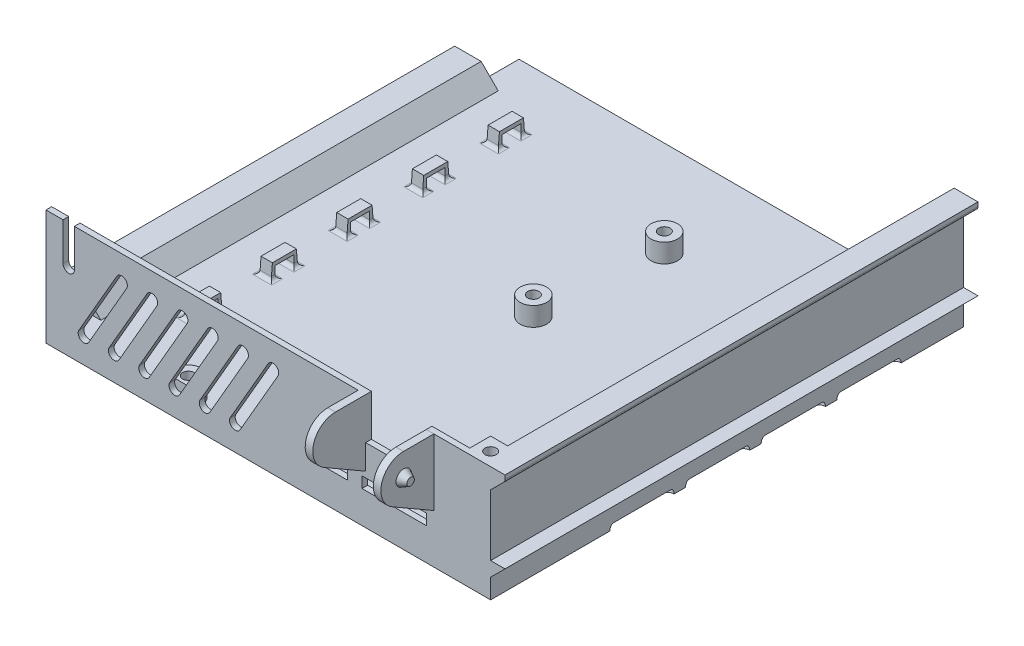
SolidWorks part; units mm, degrees
material "ABS"
ref_plane "Front Plane" through (0, 0, 0) normal (0, 0, 1) x (1, 0, 0)
ref_plane "Top Plane" through (0, 0, 0) normal (0, 1, 0) x (1, 0, 0)
ref_plane "Right Plane" through (0, 0, 0) normal (1, 0, 0) x (0, 0, -1)
ref_axis "Axis1" through (0, 0, 22) along (0, 0, -1)
sketch "Sketch1" plane through (0, 0, 0) normal (0, 1, 0) x (1, 0, 0)
  line L0 (-124.5, 0) -> (0, 0) construction
  line L1 (124.5, 0) -> (124.5, 125) construction
  line L2 (124.5, 125) -> (-124.5, 125) construction
  line L3 (-124.5, 125) -> (-124.5, 0) construction
  line L4 (40.75, 3.85) -> (40.75, 1.6) construction
  line L5 (38.5, 101.6) -> (108.5, 101.6)
  line L6 (38.5, 101.6) -> (38.5, 1.6)
  line L7 (38.5, 1.6) -> (108.5, 1.6)
  line L8 (108.5, 101.6) -> (108.5, 1.6)
  line L9 (38.5, 101.6) -> (108.5, 1.6) construction
  line L10 (38.5, 1.6) -> (108.5, 101.6) construction
  line L11 (40.75, 3.85) -> (38.5, 3.85) construction
  line L12 (-113.79, 77.51) -> (-116.04, 77.51) construction
  line L13 (77.7, 11.6) -> (86.7, 11.6)
  line L14 (77.7, 11.6) -> (77.7, 1.6)
  line L15 (77.7, 1.6) -> (86.7, 1.6)
  line L16 (86.7, 11.6) -> (86.7, 1.6)
  line L17 (77.7, 11.6) -> (86.7, 1.6) construction
  line L18 (77.7, 1.6) -> (86.7, 11.6) construction
  line L19 (90.5, 16.6) -> (107.5, 16.6)
  line L20 (90.5, 16.6) -> (90.5, 1.6)
  line L21 (90.5, 1.6) -> (107.5, 1.6)
  line L22 (107.5, 16.6) -> (107.5, 1.6)
  line L23 (90.5, 16.6) -> (107.5, 1.6) construction
  line L24 (90.5, 1.6) -> (107.5, 16.6) construction
  line L25 (-116.04, 113.59) -> (-92.96, 113.59)
  line L26 (-116.04, 113.59) -> (-116.04, 71.41)
  line L27 (-116.04, 71.41) -> (-92.96, 71.41)
  line L28 (-92.96, 113.59) -> (-92.96, 71.41)
  line L29 (-116.04, 113.59) -> (-92.96, 71.41) construction
  line L30 (-116.04, 71.41) -> (-92.96, 113.59) construction
  line L31 (-113.79, 77.51) -> (-113.79, 71.41) construction
  line L32 (-95.21, 107.49) -> (-95.21, 113.59) construction
  line L33 (-95.21, 107.49) -> (-92.96, 107.49) construction
  line L34 (-64.5, 85.45) -> (-68, 85.45) construction
  line L35 (-65, 88.95) -> (-15, 88.95)
  line L36 (-68, 85.95) -> (-68, 6.95)
  line L37 (-65, 3.95) -> (-15, 3.95)
  line L38 (-12, 85.95) -> (-12, 6.95)
  line L39 (-68, 88.95) -> (-12, 3.95) construction
  line L40 (-68, 3.95) -> (-12, 88.95) construction
  line L41 (-64.5, 85.45) -> (-15.5, 85.45) construction
  line L42 (-64.5, 85.45) -> (-64.5, 27.45) construction
  line L43 (-64.5, 27.45) -> (-15.5, 27.45) construction
  line L44 (-15.5, 85.45) -> (-15.5, 27.45) construction
  line L45 (0, 0) -> (0, 125) construction
  line L46 (0, 0) -> (124.5, 0) construction
  line L47 (-64.5, 85.45) -> (-64.5, 88.95) construction
  line L48 (73.5, 0.1) -> (73.5, 125) construction
  line L49 (-65.69, 22.9) -> (-49.81, 22.9)
  line L50 (-65.69, 22.9) -> (-65.69, 1.5)
  line L51 (-65.69, 1.5) -> (-49.81, 1.5)
  line L52 (-49.81, 22.9) -> (-49.81, 1.5)
  line L53 (-65.69, 22.9) -> (-49.81, 1.5) construction
  line L54 (-65.69, 1.5) -> (-49.81, 22.9) construction
  line L55 (-45.65, 19.42) -> (-32.35, 19.42)
  line L56 (-45.65, 19.42) -> (-45.65, 1.5)
  line L57 (-45.65, 1.5) -> (-32.35, 1.5)
  line L58 (-32.35, 19.42) -> (-32.35, 1.5)
  line L59 (-45.65, 19.42) -> (-32.35, 1.5) construction
  line L60 (-45.65, 1.5) -> (-32.35, 19.42) construction
  line L61 (-27.65, 19.42) -> (-14.35, 19.42)
  line L62 (-27.65, 19.42) -> (-27.65, 1.5)
  line L63 (-27.65, 1.5) -> (-14.35, 1.5)
  line L64 (-14.35, 19.42) -> (-14.35, 1.5)
  line L65 (-27.65, 19.42) -> (-14.35, 1.5) construction
  line L66 (-27.65, 1.5) -> (-14.35, 19.42) construction
  line L67 (-40, 0) -> (-40, 125) construction
  line L68 (-113.79, 11.41) -> (-113.79, 17.51) construction
  line L69 (-116.04, 53.59) -> (-92.96, 53.59)
  line L70 (-116.04, 53.59) -> (-116.04, 11.41)
  line L71 (-116.04, 11.41) -> (-92.96, 11.41)
  line L72 (-92.96, 53.59) -> (-92.96, 11.41)
  line L73 (-116.04, 53.59) -> (-92.96, 11.41) construction
  line L74 (-116.04, 11.41) -> (-92.96, 53.59) construction
  line L75 (-113.79, 17.51) -> (-116.04, 17.51) construction
  line L76 (-95.21, 53.59) -> (-95.21, 47.49) construction
  line L77 (-95.21, 47.49) -> (-92.96, 47.49) construction
  line L78 (-104.5, 0) -> (-104.5, 32.5) construction
  line L79 (-104.5, 32.5) -> (-104.5, 92.5) construction
  line L80 (-104.5, 92.5) -> (-104.5, 125) construction
  line L81 (-64.5, 27.45) -> (-15.5, 85.45) construction
  line L82 (-15.5, 27.45) -> (-64.5, 85.45) construction
  circle A0 centre (105.5, 81.6) radius 1.75
  circle A1 centre (105.5, 19.6) radius 1.75
  circle A2 centre (70.6, 99.8) radius 1.75
  circle A3 centre (67.8, 68) radius 1.75
  circle A4 centre (40.75, 3.85) radius 1.75
  circle A5 centre (-95.21, 107.49) radius 1.4
  circle A6 centre (-113.79, 77.51) radius 1.4
  arc A7 (-15, 3.95) -> (-12, 6.95) centre (-15, 6.95) ccw
  arc A8 (-68, 6.95) -> (-65, 3.95) centre (-65, 6.95) ccw
  arc A9 (-15, 88.95) -> (-12, 85.95) centre (-15, 85.95) cw
  arc A10 (-65, 88.95) -> (-68, 85.95) centre (-65, 85.95) ccw
  circle A11 centre (-64.5, 85.45) radius 1.375
  circle A12 centre (-15.5, 85.45) radius 1.375
  circle A13 centre (-64.5, 27.45) radius 1.375
  circle A14 centre (-15.5, 27.45) radius 1.375
  circle A15 centre (-95.21, 47.49) radius 1.4
  circle A16 centre (-113.79, 17.51) radius 1.4
  circle A17 centre (40.75, 3.85) radius 2.84
  point P0 (73.5, 51.6)
  point P3 (-104.5, 92.5)
  point P4 (0, 0)
  point P24 (82.2, 6.6)
  point P30 (99, 9.1)
  point P47 (-40, 46.45)
  point P65 (-39, 10.46)
  point P69 (-57.75, 12.2)
  point P84 (-21, 10.46)
  point P89 (-104.5, 32.5)
  point P111 (-40, 56.45)
  dimension "D5" = 3.5
  dimension "D26" = 3
  dimension "D27" = 2.75
  dimension "D44" = 2.8
  dimension "D49" = 5.68
  dimension "D1" = 249
  dimension "D2" = 125
  dimension "D3" = 100
  dimension "D4" = 70
  dimension "D6" = 20
  dimension "D7" = 3
  dimension "D8" = 82
  dimension "D9" = 1.8
  dimension "D10" = 37.9
  dimension "D11" = 33.6
  dimension "D12" = 40.7
  dimension "D13" = 2.25
  dimension "D14" = 9
  dimension "D15" = 10
  dimension "D16" = 26.3
  dimension "D17" = 17
  dimension "D18" = 15
  dimension "D19" = 9.5
  dimension "D20" = 23.08
  dimension "D21" = 42.18
  dimension "D22" = 6.1
  dimension "D23" = 2.25
  dimension "D24" = 85
  dimension "D25" = 56
  dimension "D28" = 58
  dimension "D29" = 49
  dimension "D30" = 10.25
  dimension "D31" = 29
  dimension "D32" = 47
  dimension "D33" = 21.4
  dimension "D34" = 15.88
  dimension "D35" = 2.45
  dimension "D36" = 13.3
  dimension "D37" = 17.92
  dimension "D38" = 2.45
  dimension "D39" = 2.45
  dimension "D40" = 2.25
  dimension "D41" = 1.6
  dimension "D42" = 40
  dimension "D43" = 1.5
  dimension "D45" = 60
  dimension "D46" = 3.5
  dimension "D47" = 20
  dimension "D48" = 16
sketch "Sketch2" plane through (0, 0, 0) normal (0, 1, 0) x (1, 0, 0)
  line L0 (124.5, 125) -> (-124.5, 125) construction
  line L1 (124.5, 0) -> (7, 0)
  line L2 (124.5, 0) -> (124.5, 125)
  line L3 (124.5, 125) -> (7, 125)
  line L4 (7, 0) -> (7, 125)
  line L5 (124.5, 0) -> (7, 125) construction
  line L6 (124.5, 125) -> (7, 0) construction
  point P4 (65.75, 62.5)
  dimension "D1" = 7
extrude "Boss-Extrude1" add sketch "Sketch2" along normal blind 2.5
sketch "Sketch3" plane through (0, 2.5, 0) normal (0, 1, 0) x (1, 0, 0)
  circle A0 centre (105.5, 19.6) radius 1.5
  circle A1 centre (67.8, 68) radius 1.5
  circle A2 centre (105.5, 81.6) radius 1.5
  circle A3 centre (70.6, 99.8) radius 1.5
  circle A4 centre (40.75, 3.85) radius 1.5
  circle A5 centre (40.75, 3.85) radius 3.5
  circle A6 centre (105.5, 19.6) radius 3.5
  circle A7 centre (67.8, 68) radius 3.5
  circle A8 centre (105.5, 81.6) radius 3.5
  circle A9 centre (70.6, 99.8) radius 3.5
  dimension "D1" = 3
  dimension "D2" = 2
extrude "Boss-Extrude2" add sketch "Sketch3" along normal blind 5
sketch "Sketch5" plane through (0, 2.5, 0) normal (0, 1, 0) x (1, 0, 0)
  line L0 (124.5, 0) -> (124.5, 125) construction
  line L1 (7, 0) -> (124.5, 0)
  line L2 (7, 0) -> (7, 1.5)
  line L3 (7, 1.5) -> (124.5, 1.5)
  line L4 (124.5, 0) -> (124.5, 1.5)
  line L5 (7, 0) -> (124.5, 1.5) construction
  line L6 (7, 1.5) -> (124.5, 0) construction
  point P4 (65.75, 0.75)
  dimension "D1" = 1.5
extrude "Boss-Extrude3" add sketch "Sketch5" along normal blind 28
sketch "Sketch6" plane through (0, 0, 0) normal (0, 0, 1) x (1, 0, 0)
  line L0 (77.7, 0) -> (86.7, 0) construction
  line L1 (77.7, 0) -> (86.7, 0) construction
  line L2 (90.5, 0) -> (107.5, 0) construction
  line L3 (90.5, 0) -> (107.5, 0) construction
  line L4 (77.7, 0) -> (77.7, 2.5) construction
  line L5 (77.7, 2.5) -> (77.7, 7.5) construction
  line L6 (77.7, 7.5) -> (77.7, 8.5) construction
  line L7 (77.7, 8.5) -> (86.7, 8.5)
  line L8 (86.7, 8.5) -> (86.7, 13.6)
  line L9 (86.7, 13.6) -> (77.7, 13.6)
  line L10 (77.7, 13.6) -> (77.7, 8.5)
  line L11 (90.5, 8.5) -> (107.5, 8.5)
  line L12 (107.5, 8.5) -> (107.5, 11.4)
  line L13 (107.5, 11.4) -> (90.5, 11.4)
  line L14 (90.5, 11.4) -> (90.5, 8.5)
  line L15 (77.7, 8.5) -> (86.7, 13.6) construction
  line L16 (77.7, 13.6) -> (86.7, 8.5) construction
  line L18 (76.45, 15.8) -> (87.95, 15.8) construction
  line L19 (76.45, 15.8) -> (76.45, 6.3) construction
  line L20 (76.45, 6.3) -> (87.95, 6.3) construction
  line L21 (87.95, 15.8) -> (87.95, 6.3) construction
  line L22 (76.45, 15.8) -> (87.95, 6.3) construction
  line L23 (76.45, 6.3) -> (87.95, 15.8) construction
  point P9 (82.2, 11.05)
  dimension "D1" = 2.5
  dimension "D2" = 5
  dimension "D3" = 1
  dimension "D4" = 9
  dimension "D5" = 17
  dimension "D6" = 2.9
  dimension "D7" = 5.1
  dimension "D8" = 11.5
  dimension "D9" = 9.5
extrude "Cut-Extrude1" cut sketch "Sketch6" against normal up to surface (1.5 mm away) up to face at (53.25, 10.75, -1.5)
sketch "Sketch7" plane through (0, 0, 0) normal (0, 0, 1) x (1, 0, 0)
  line L0 (124.5, 0) -> (124.5, 5.2)
  line L1 (124.5, 30.5) -> (124.5, 0) construction
  line L2 (124.5, 5.2) -> (126.3, 7)
  line L3 (126.3, 7) -> (126.3, 0) construction
  line L4 (126.3, 0) -> (124.5, 0) construction
  line L5 (126.3, 7) -> (122, 7)
  line L6 (122, 7) -> (122, 0)
  line L7 (7, 0) -> (124.5, 0) construction
  line L8 (122, 0) -> (124.5, 0)
  line L9 (124.5, 7) -> (124.5, 25.2)
  line L10 (126.3, 7) -> (126.3, 27) construction
  line L11 (124.5, 25.2) -> (126.3, 27)
  line L12 (126.3, 0) -> (128.3, 0) construction
  line L13 (128.3, 0) -> (128.3, 29) construction
  line L14 (126.3, 7) -> (128.3, 9)
  line L15 (126.3, 27) -> (128.3, 29)
  line L16 (122, 7) -> (122, 30.5)
  line L17 (7, 30.5) -> (124.5, 30.5) construction
  line L18 (122, 30.5) -> (128.3, 30.5)
  line L19 (128.3, 30.5) -> (128.3, 29)
  line L20 (128.3, 9) -> (122, 9)
  line M19 (7, 0) -> (124.5, 0)
  line M20 (124.5, 0) -> (124.5, 30.5)
  line M21 (124.5, 30.5) -> (7, 30.5)
  dimension "D1" = 5.2
  dimension "D2" = 7
  dimension "D3" = 1.8
  dimension "D4" = 2.5
  dimension "D5" = 25.2
  dimension "D6" = 27
  dimension "D7" = 2
extrude "Boss-Extrude4" add sketch "Sketch7" against normal up to surface (125 mm away) contours L5 L6 M19 M20 | L2 L5 M20 | L14 L20 L5 M20 | L20 L16 L5 M20 | L20 L9 L16 M20 M21 | L19 L18 L11 L15 M20 region at (123.25, 3.5, 0) region at (125.1, 6.4, 0) region at (125.9595, 8.119, 0) region at (123.25, 8, 0) region at (123.25, 19.75, 0) region at (126.0461, 28.623, 0) up to face at (65.75, 1.25, -125)
fillet "Fillet1" radius 1 1 edges at (128.3, 29, -62.5)
sketch "Sketch9" plane through (0, 0, 0) normal (0, 0, 1) x (1, 0, 0)
  line L0 (7, 7) -> (11.5, 2.5)
  line L1 (7, 0) -> (0, 0)
  line L2 (7, 0) -> (7, 7)
  line L3 (7, 7) -> (0, 7)
  line L4 (0, 0) -> (0, 7)
  line L5 (7, 0) -> (0, 7) construction
  line L6 (7, 7) -> (0, 0) construction
  line L7 (11.5, 2.5) -> (7, 2.5)
  line L8 (7, 0) -> (124.5, 0) construction
  circle A0 centre (3.5, 3.5) radius 1.5
  point P4 (3.5, 3.5)
  line M15 (7, 30.5) -> (7, 0)
  dimension "D2" = 3
  dimension "D1" = 7
  dimension "D3" = 2.5
  dimension "D4" = 45
extrude "Boss-Extrude5" add sketch "Sketch9" against normal offset from surface (105 mm away) 10 from offset 10 contours L4 L1 L2 L3 A0 M15 | L7 L0 M15 region at (8.5, 4, 0) region at (6.901, 4.75, 0) up to face at (105.7481, 14.3743, -125) offset against normal yes
sketch "Sketch12" plane through (0, 30.5, 0) normal (0, 1, 0) x (1, 0, 0)
  line L1 (124.5, 0) -> (117.5, 0)
  line L2 (124.5, 0) -> (124.5, 7)
  line L3 (124.5, 7) -> (117.5, 7)
  line L4 (117.5, 0) -> (117.5, 7)
  line L5 (124.5, 0) -> (117.5, 7) construction
  line L6 (124.5, 7) -> (117.5, 0) construction
  circle A0 centre (121, 3.5) radius 1.5 construction
  point P4 (121, 3.5)
  dimension "D2" = 3
  dimension "D1" = 7
extrude "Boss-Extrude7" add sketch "Sketch12" against normal up to surface (28 mm away) up to face at (37.65, 2.5, -51.185)
sketch "Sketch13" plane through (0, 30.5, 0) normal (0, 1, 0) x (1, 0, 0)
  circle A0 centre (121, 3.5) radius 1.5 construction
  circle A1 centre (121, 3.5) radius 1.5
extrude "Cut-Extrude3" cut sketch "Sketch13" against normal blind 10
sketch "Sketch15" plane through (0, 0, 0) normal (-1, 0, 0) x (0, 0, 1)
  line L0 (-125, 2.5) -> (-1.5, 2.5) construction
  line L1 (-107.5, 2.5) -> (-108.5, 2.5)
  line L2 (-107.5, 2.5) -> (-102.5, 2.5) construction
  line L3 (-107.5, 2.5) -> (-107.5, 5.5)
  line L4 (-107.5, 5.5) -> (-102.5, 5.5)
  line L5 (-102.5, 2.5) -> (-102.5, 5.5)
  line L6 (-107.5, 2.5) -> (-102.5, 5.5) construction
  line L7 (-107.5, 5.5) -> (-102.5, 2.5) construction
  line L8 (-108.5, 2.5) -> (-108.1701, 6.5)
  line L9 (-108.1701, 6.5) -> (-101.8299, 6.5)
  line L10 (-101.8299, 6.5) -> (-101.5, 2.5)
  line L11 (-101.5, 2.5) -> (-102.5, 2.5)
  line L12 (-115, 7) -> (-115, 0) construction
  point P8 (-105, 4)
  dimension "D1" = 3
  dimension "D2" = 5
  dimension "D3" = 1
  dimension "D4" = 1
  dimension "D5" = 0.75
  dimension "D6" = 10
extrude "Boss-Extrude8" add sketch "Sketch15" along normal blind 3 from offset 25 offset against normal yes
pattern_linear "LPattern1" count 5 spacing 20 along (0, 0, 1) of "Boss-Extrude8"
fillet "Fillet2" radius 1 40 edges at (25, 2.5, -62) (23.5, 2.5, -62.5) (23.5, 2.5, -61.5) (22, 2.5, -62) (25, 2.5, -68) (22, 2.5, -68) (23.5, 2.5, -67.5) (23.5, 2.5, -68.5) (25, 2.5, -82) (23.5, 2.5, -82.5) (23.5, 2.5, -81.5) (22, 2.5, -82) (25, 2.5, -88) (23.5, 2.5, -88.5) (23.5, 2.5, -87.5) (22, 2.5, -88) (25, 2.5, -102) (23.5, 2.5, -102.5) (23.5, 2.5, -101.5) (22, 2.5, -102) (25, 2.5, -108) (23.5, 2.5, -108.5) (23.5, 2.5, -107.5) (22, 2.5, -108) (25, 2.5, -22) (23.5, 2.5, -22.5) (23.5, 2.5, -21.5) (22, 2.5, -22) (25, 2.5, -28) (23.5, 2.5, -28.5) (23.5, 2.5, -27.5) (22, 2.5, -28) (25, 2.5, -42) (23.5, 2.5, -42.5) (23.5, 2.5, -41.5) (22, 2.5, -42) (25, 2.5, -48) (23.5, 2.5, -48.5) (23.5, 2.5, -47.5) (22, 2.5, -48)
sketch "Sketch16" plane through (0, 0, 0) normal (0, 0, 1) x (1, 0, 0)
  line L0 (27, 23.9103) -> (17, 6.5897) construction
  line L1 (28.299, 23.1603) -> (18.299, 5.8397)
  line L2 (25.701, 24.6603) -> (15.701, 7.3397)
  line L3 (17, 6.5897) -> (27, 6.5897) construction
  line L4 (27, 6.5897) -> (27, 23.9103) construction
  line L5 (7, 15.25) -> (124.5, 15.25) construction
  line L6 (7, 30.5) -> (7, 0) construction
  line L7 (124.5, 25.2) -> (124.5, 9) construction
  arc A0 (28.299, 23.1603) -> (25.701, 24.6603) centre (27, 23.9103) ccw
  arc A1 (15.701, 7.3397) -> (18.299, 5.8397) centre (17, 6.5897) ccw
  point P2 (22, 15.25)
  dimension "D3" = 1.5
  dimension "D1" = 60
  dimension "D2" = 20
  dimension "D4" = 15
extrude "Cut-Extrude4" cut sketch "Sketch16" against normal up to surface (1.5 mm away) up to face at (82.2, 11.05, -1.5)
pattern_linear "LPattern2" count 6 spacing 8 along (1, 0, 0) of "Cut-Extrude4"
ref_plane "Plane2" through (59.75, -59.75, 0) normal (-0.7071, 0.7071, 0) x (0, 0, 1)
sketch "Sketch18" plane through (59.75, -59.75, 0) normal (-0.7071, 0.7071, 0) x (0, 0, 1)
  line L0 (-107.5, 88.0348) -> (-92.5, 88.0348) construction
  line L1 (-125, 88.0348) -> (-7, 88.0348) construction
  line L2 (-107.5, 89.0348) -> (-92.5, 89.0348)
  line L3 (-107.5, 87.0348) -> (-92.5, 87.0348)
  arc A0 (-107.5, 89.0348) -> (-107.5, 87.0348) centre (-107.5, 88.0348) ccw
  arc A1 (-92.5, 87.0348) -> (-92.5, 89.0348) centre (-92.5, 88.0348) ccw
  point P4 (-100, 88.0348)
  dimension "D1" = 15
  dimension "D2" = 1
  dimension "D3" = 25
extrude "Cut-Extrude5" cut sketch "Sketch18" against normal through all both and the other way through all
pattern_linear "LPattern3" count 4 spacing 20 along (0, 0, 1) of "Cut-Extrude5"
ref_plane "Plane3" through (99.5, 0, 0) normal (1, 0, 0) x (0, 0, -1)
ref_plane "Plane4" through (109.5, 0, 0) normal (1, 0, 0) x (0, 0, -1)
sketch "Sketch20" plane through (109.5, 0, 0) normal (1, 0, 0) x (0, 0, -1)
  line L0 (0, 25.2) -> (0, 9) construction
  line L1 (125, 30.5) -> (0, 30.5) construction
  line L2 (-8, 30.5) -> (0, 30.5)
  line L3 (-11, 19.3038) -> (0, 12.953)
  line L4 (0, 30.5) -> (0, 12.953)
  arc A0 (-8, 30.5) -> (-11, 19.3038) centre (-8, 24.5) ccw
  dimension "D1" = 12
  dimension "D3" = 60
  dimension "D2" = 8
extrude "Boss-Extrude9" add sketch "Sketch20" against normal blind 2 separate body
ref_plane "Plane5" through (0, 0, 8) normal (0, 0, 1) x (1, 0, 0)
sketch "Sketch24" plane through (0, 0, 8) normal (0, 0, 1) x (1, 0, 0)
  line L0 (109.5, 24.5) -> (111.34, 24.5)
  line L1 (111.34, 24.5) -> (111.34, 25.5)
  line L2 (111.34, 25.5) -> (109.5, 26.5)
  line L3 (109.5, 26.5) -> (109.5, 24.5)
  dimension "D1" = 1.84
  dimension "D2" = 2
  dimension "D3" = 1
revolve "Revolve1" add sketch "Sketch24" angle 360 about L0
mirror "Mirror2" about plane through (99.5, 0, 0) normal (1, 0, 0) of "Revolve1", "Boss-Extrude9"
sketch "Sketch25" plane through (0, 0, 0) normal (0, 0, 1) x (1, 0, 0)
  line L0 (107.5, 30.5) -> (107.5, 19.3038) construction
  line L1 (91.5, 30.5) -> (107.5, 30.5)
  line L2 (91.5, 30.5) -> (91.5, 19.5)
  line L3 (91.5, 19.5) -> (107.5, 19.5)
  line L4 (107.5, 30.5) -> (107.5, 19.5)
  line L5 (91.5, 30.5) -> (107.5, 19.5) construction
  line L6 (91.5, 19.5) -> (107.5, 30.5) construction
  point P4 (99.5, 25)
  dimension "D1" = 11
extrude "Cut-Extrude6" cut sketch "Sketch25" against normal up to surface (1.5 mm away) up to face at (38, 15.25, -1.5)
sketch "Sketch26" plane through (0, 0, 0) normal (0, 0, 1) x (1, 0, 0)
  line L0 (13, 30.5) -> (13, 20.5) construction
  line L1 (7, 30.5) -> (89.5, 30.5) construction
  line L2 (14.5, 30.5) -> (14.5, 20.5)
  line L3 (11.5, 30.5) -> (11.5, 20.5)
  line L4 (7, 30.5) -> (7, 0) construction
  line L5 (11.5, 30.5) -> (14.5, 30.5)
  arc A0 (14.5, 30.5) -> (11.5, 30.5) centre (13, 30.5) ccw
  arc A1 (11.5, 20.5) -> (14.5, 20.5) centre (13, 20.5) ccw
  point P4 (13, 25.5)
  line M41 (89.5, 30.5) -> (7, 30.5)
  dimension "D1" = 10
  dimension "D2" = 1.5
  dimension "D3" = 6
extrude "Cut-Extrude7" cut sketch "Sketch26" against normal up to surface (1.5 mm away) contours L3 A1 L2 L5 M41 region at (13, 24.9059, 0) up to face at (62.2376, 15.6325, -1.5)
equation "\"D16@Sketch1\"=22.8+3.5"
equation "\"D19@Sketch1\"=6+3.5"
equation "\"D1@Boss-Extrude3\"=33-2.5-2.5"
